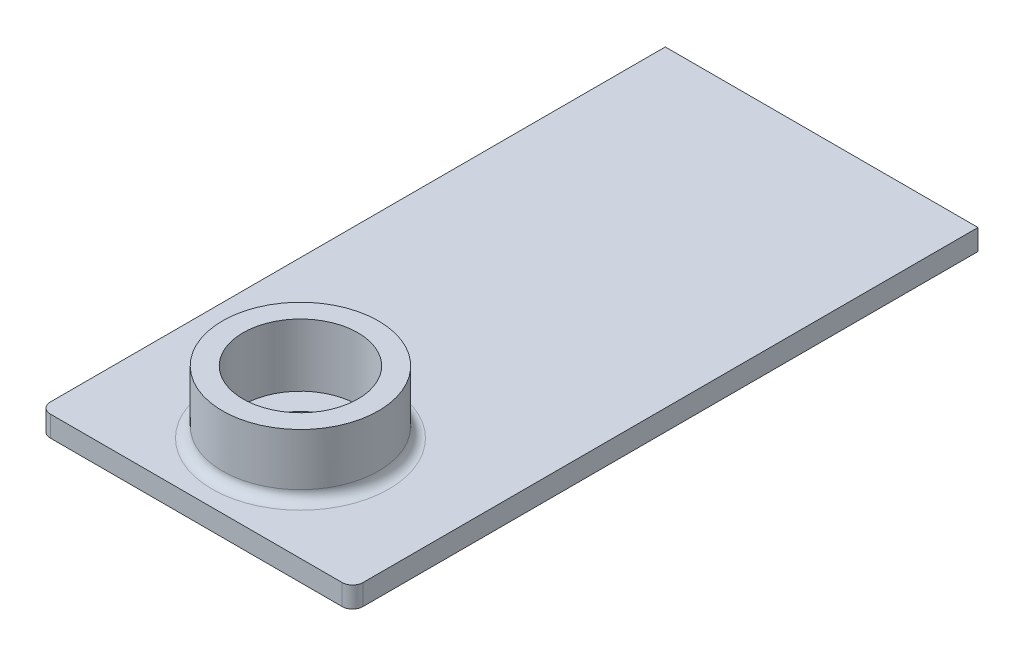
SolidWorks part; units mm, degrees
ref_plane "Front Plane" through (0, 0, 0) normal (0, 0, 1) x (1, 0, 0)
ref_plane "Top Plane" through (0, 0, 0) normal (0, 1, 0) x (1, 0, 0)
ref_plane "Right Plane" through (0, 0, 0) normal (1, 0, 0) x (0, 0, -1)
sketch "Sketch1" plane through (0, 0, 0) normal (0, 1, 0) x (1, 0, 0)
  line L0 (0, 0) -> (38.1, 0)
  line L1 (38.1, 0) -> (38.1, 76.2)
  line L2 (38.1, 76.2) -> (0, 76.2)
  line L3 (0, 76.2) -> (0, 0)
  dimension "D1" = 38.1
  dimension "D2" = 76.2
extrude "Boss-Extrude1" add sketch "Sketch1" along normal mid plane 2.54 contours L3 L0 L1 L2
sketch "Sketch3" plane through (0, 1.27, 0) normal (0, 1, 0) x (1, 0, 0)
  line L0 (19.05, 0) -> (19.05, 12.7)
  line L1 (0, 0) -> (38.1, 0) construction
  circle A0 centre (19.05, 12.7) radius 7
  circle A1 centre (19.05, 12.7) radius 9.5
  circle A2 centre (19.05, 12.7) radius 4
  dimension "D2" = 14
  dimension "D3" = 2.5
  dimension "D4" = 8
  dimension "D1" = 12.7
extrude "Boss-Extrude2" add sketch "Sketch3" along normal blind 7.62 contours A1 A0 region at (12.5225, 1.27, -19.2275)
extrude "Cut-Extrude2" cut sketch "Sketch3<5>" against normal blind 7.62 contours A2 region at (16.3016, 1.27, -15.4484)
sketch "Sketch3<5>" plane through (0, 1.27, 0) normal (0, 1, 0) x (1, 0, 0) same geometry as "Sketch3"
fillet "Fillet1" radius 1.27 1 edges at (19.05, 1.27, -3.2)
fillet "Fillet2" radius 1.27 2 edges at (38.1, 0, 0) (0, 0, 0)
